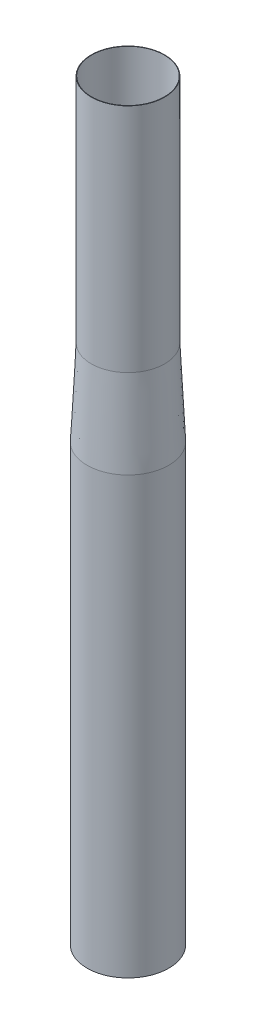
SolidWorks part; units mm, degrees
material "Ceramic Porcelain"
ref_plane "Front" through (0, 0, 0) normal (0, 0, 1) x (1, 0, 0)
ref_plane "Top" through (0, 0, 0) normal (0, 1, 0) x (1, 0, 0)
ref_plane "Right" through (0, 0, 0) normal (1, 0, 0) x (0, 0, -1)
ref_plane "Plane1" through (0, 5791.2, 0) normal (0, 1, 0) x (1, 0, 0)
sketch "Sketch1" plane through (0, 0, 0) normal (0, 1, 0) x (1, 0, 0)
  circle A0 centre (0, 0) radius 311.15
  circle A1 centre (0, 0) radius 314.325
  dimension "D1" = 622.3
  dimension "D2" = 628.65
extrude "Boss-Extrude1" add sketch "Sketch1" along normal blind 3352.8
sketch "Sketch2" plane through (0, 0, 0) normal (0, 0, 1) x (1, 0, 0)
  line L0 (0, 3352.8) -> (0, 5791.2) construction
  line L1 (314.325, 3352.8) -> (-314.325, 3352.8) construction
  line L2 (625.8511, 5791.2) -> (-625.8511, 5791.2) construction
  line L3 (-314.325, 3352.8) -> (-282.5713, 4013.2)
  line L4 (-282.5713, 4013.2) -> (-282.5713, 5791.2)
  line L5 (-282.5713, 5791.2) -> (-279.4, 5791.2)
  line L6 (-279.4, 5791.2) -> (-279.4, 4013.1238)
  line L7 (-279.4, 4013.1238) -> (-311.15, 3352.8)
  line L8 (-311.15, 3352.8) -> (-314.325, 3352.8)
  line L9 (-279.4, 4013.1238) -> (-282.5713, 4013.1238) construction
  line L11 (-282.5713, 4013.2) -> (-279.4037, 4013.0477) construction
  dimension "D1" = 558.8
  dimension "D2" = 1778
revolve "Revolve1" add sketch "Sketch2" angle 360 about L0
